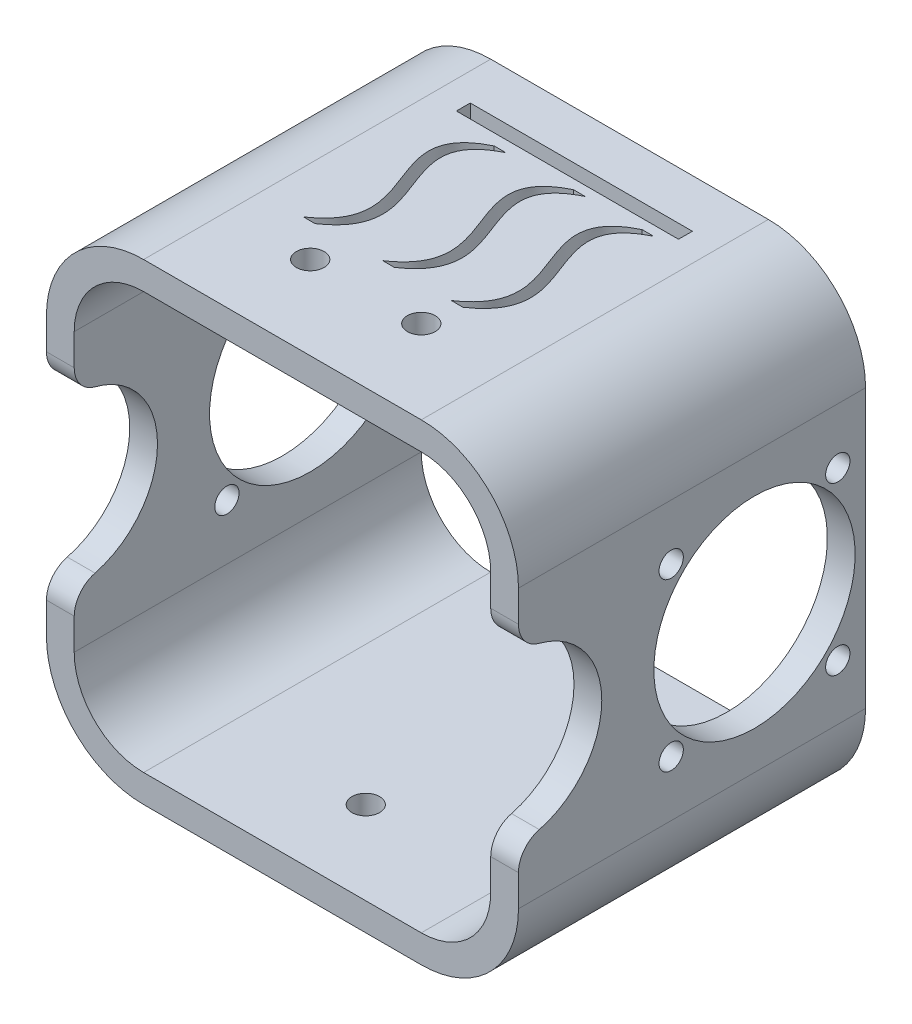
SolidWorks part; units mm, degrees
ref_plane "Piano frontale" through (0, 0, 0) normal (0, 0, 1) x (1, 0, 0)
ref_plane "Piano superiore" through (0, 0, 0) normal (0, 1, 0) x (1, 0, 0)
ref_plane "Piano destro" through (0, 0, 0) normal (1, 0, 0) x (0, 0, -1)
sketch "Schizzo1" plane through (0, 0, 0) normal (0, 0, 1) x (1, 0, 0)
  line L0 (-10, 0) -> (-50, 0)
  line L1 (0, -10) -> (0, -50)
  line L2 (-60, -10) -> (-60, -50)
  line L3 (-50, -60) -> (-10, -60)
  arc A0 (0, -50) -> (-10, -60) centre (-10, -50) cw
  arc A1 (-50, -60) -> (-60, -50) centre (-50, -50) cw
  arc A2 (0, -10) -> (-10, 0) centre (-10, -10) ccw
  arc A3 (-60, -10) -> (-50, 0) centre (-50, -10) cw
  point P7 (0, -60)
  point P10 (-60, -60)
  point P13 (0, 0)
  point P16 (-60, 0)
  dimension "D4" = 10
  dimension "D1" = 60
  dimension "D2" = 60
  dimension "D3" = 60
extrude "Estrusione-Sottile1" add sketch "Schizzo1" along normal blind 50 thin thin type one direction wall 4
sketch "Schizzo2" plane through (0, 4, 0) normal (0, 1, 0) x (1, 0, 0)
  line L0 (-30, 0) -> (-30, -50) construction
  line L1 (-10, 0) -> (-50, 0) construction
  line L2 (-10, -50) -> (-50, -50) construction
  circle A0 centre (-38, -38) radius 2
  circle A1 centre (-22, -38) radius 2
  dimension "D5" = 4
  dimension "D6" = 4
  dimension "D1" = 8
  dimension "D2" = 8
  dimension "D3" = 12
  dimension "D4" = 12
extrude "Taglio-Estrusione1" cut sketch "Schizzo2" against normal blind 10
sketch "Schizzo3" plane through (-64, 0, 0) normal (-1, 0, 0) x (0, 0, 1)
  line L0 (50, -10) -> (50, -50) construction
  circle A0 centre (50, -30) radius 12
  dimension "D1" = 24
extrude "Taglio-Estrusione2" cut sketch "Schizzo3" along direction (-1, 0, 0) on the side against the normal up to surface (68 mm away) up to face at (4, -30, 25)
fillet "Raccordo1" radius 4 1 edges at (-62, -18, 50) type face fillet first side face at (-30, -7.8382, 50) second side face at (-62, -30, 44)
fillet "Raccordo2" radius 4 1 edges at (-62, -42, 50) type face fillet first side face at (-62, -30.8513, 43.2978) second side face at (-30, -52.1618, 50)
fillet "Raccordo3" radius 4 1 edges at (2, -18, 50) type face fillet first side face at (2, -30, 44) second side face at (-30, -7.2563, 50)
fillet "Raccordo4" radius 4 1 edges at (2, -42, 50) type face fillet first side face at (2, -30.8513, 43.2978) second side face at (-30, -52.7437, 50)
sketch "Schizzo4" plane through (0, -64, 0) normal (0, -1, 0) x (1, 0, 0)
  line L0 (-30, 50) -> (-30, 0) construction
  line L1 (-50, 50) -> (-10, 50) construction
  line L2 (-50, 0) -> (-10, 0) construction
  circle A0 centre (-30, 38) radius 2
  dimension "D1" = 4
  dimension "D2" = 12
extrude "Taglio-Estrusione3" cut sketch "Schizzo4" against normal blind 10
sketch "Schizzo5" plane through (0, 4, 0) normal (0, 1, 0) x (1, 0, 0)
  line L0 (-30, 0) -> (-30, -50) construction
  line L1 (-46, -6.9458) -> (-14, -6.9458)
  line L2 (-46, -6.9458) -> (-46, -8.9458)
  line L3 (-46, -8.9458) -> (-14, -8.9458)
  line L4 (-14, -6.9458) -> (-14, -8.9458)
  line L5 (-10, 0) -> (-50, 0) construction
  line L6 (-10, -50) -> (-50, -50) construction
  line L7 (-30.9605, -32.9287) -> (-32.6391, -32.9195)
  line L8 (-26.0641, -10.3322) -> (-27.7428, -10.3231)
  line L9 (-42.1357, -33.1817) -> (-43.8144, -33.1725)
  line L10 (-37.2394, -10.5852) -> (-38.918, -10.576)
  line L11 (-21.0473, -32.9631) -> (-22.7259, -32.9539)
  line L12 (-16.1509, -10.3666) -> (-17.8296, -10.3574)
  spline S0 degree 3 poles (-16.1509, -10.3666) (-27.5731, -15.9557) (-10.2901, -25.7029) (-21.0473, -32.9631) knots 0 0 0 0 1 1 1 1
  spline S1 degree 3 poles (-17.8296, -10.3574) (-29.2518, -15.9465) (-11.9688, -25.6937) (-22.7259, -32.9539) knots 0 0 0 0 1 1 1 1
  spline S2 degree 3 poles (-26.0641, -10.3322) (-37.4863, -15.9213) (-20.2033, -25.6686) (-30.9605, -32.9287) knots 0 0 0 0 1 1 1 1
  spline S3 degree 3 poles (-27.7428, -10.3231) (-39.1649, -15.9122) (-21.882, -25.6594) (-32.6391, -32.9195) knots 0 0 0 0 1 1 1 1
  spline S4 degree 3 poles (-37.2394, -10.5852) (-48.6615, -16.1743) (-31.3786, -25.9215) (-42.1357, -33.1817) knots 0 0 0 0 1 1 1 1
  spline S5 degree 3 poles (-38.918, -10.576) (-50.3402, -16.1651) (-33.0573, -25.9123) (-43.8144, -33.1725) knots 0 0 0 0 1 1 1 1
  dimension "D1" = 16
  dimension "D2" = 16
  dimension "D3" = 2
extrude "Taglio-Estrusione4" cut sketch "Schizzo5" against normal blind 10
sketch "Schizzo7" plane through (-64, 0, 0) normal (-1, 0, 0) x (0, 0, 1)
  line L0 (0, -30) -> (38, -30) construction
  line L1 (0, -10) -> (0, -50) construction
  line L2 (0, -18) -> (47.951, -18) construction
  line L3 (0, -42) -> (47.951, -42) construction
  line L4 (16, -18) -> (16, -42) construction
  arc A0 (47, -18.381) -> (47, -41.619) centre (50, -30) ccw construction
  arc A1 (47, -18.381) -> (50, -14.5081) centre (46, -14.5081) ccw construction
  arc A2 (50, -45.4919) -> (47, -41.619) centre (46, -45.4919) ccw construction
  circle A3 centre (28, -18) radius 1.75
  circle A4 centre (28, -42) radius 1.75
  circle A5 centre (4, -42) radius 1.75
  circle A6 centre (4, -18) radius 1.75
  dimension "D4" = 3.5
  dimension "D1" = 12
  dimension "D2" = 12
  dimension "D3" = 16
  dimension "D5" = 12
extrude "Taglio-Estrusione5" cut sketch "Schizzo7" against normal up to surface (68 mm away) up to face at (4, -30, 35.7906)
sketch "Schizzo8" plane through (-64, 0, 0) normal (-1, 0, 0) x (0, 0, 1)
  circle A0 centre (16, -30) radius 14.5
extrude "Taglio-Estrusione6" cut sketch "Schizzo8" against normal up to surface (68 mm away) up to face at (4, -19.75, 4)
